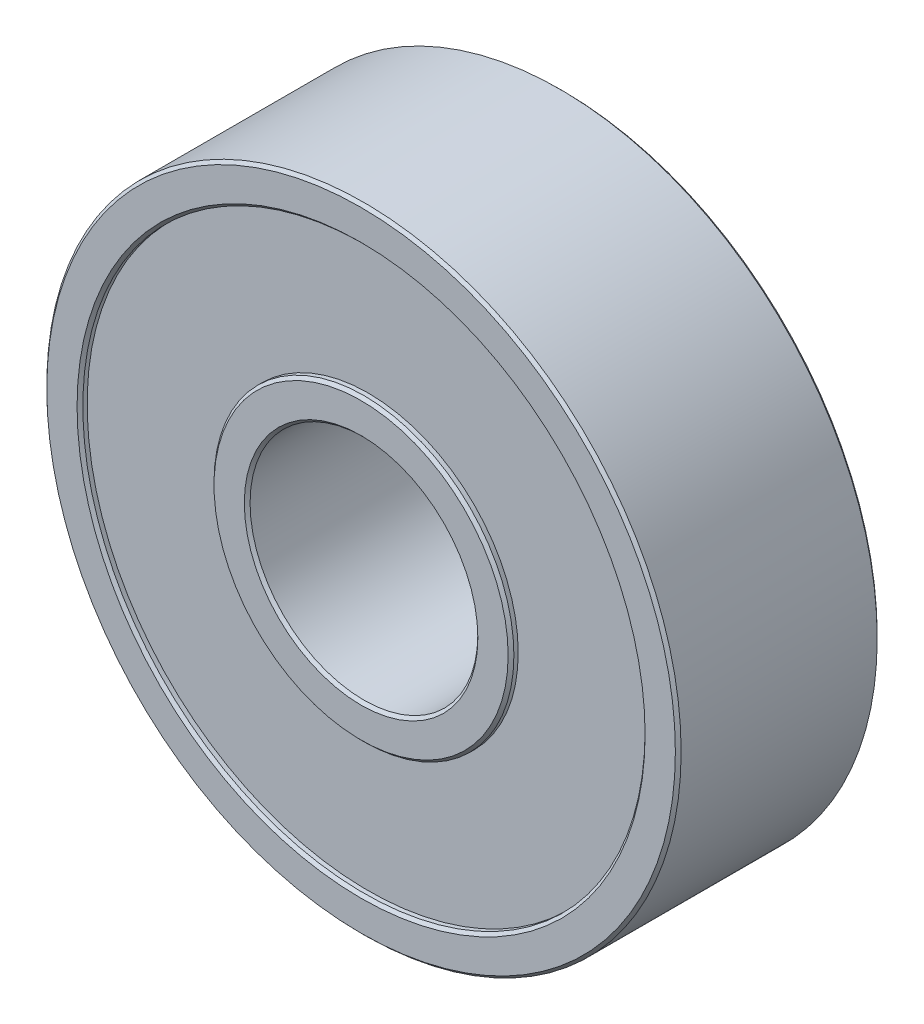
SolidWorks part; units mm, degrees
ref_plane "Front Plane" through (0, 0, 0) normal (0, 0, 1) x (1, 0, 0)
ref_plane "Top Plane" through (0, 0, 0) normal (0, 1, 0) x (1, 0, 0)
ref_plane "Right Plane" through (0, 0, 0) normal (1, 0, 0) x (0, 0, -1)
sketch "Sketch1" plane through (0, 0, 0) normal (0, 0, 1) x (1, 0, 0)
  circle A0 centre (0, 0) radius 3.95
  circle A1 centre (0, 0) radius 11
  dimension "D1" = 7.9
  dimension "D2" = 22
extrude "Boss-Extrude1" add sketch "Sketch1" along normal blind 3.5 and the other way blind 3.5
sketch "Sketch2" plane through (0, 0, 0) normal (0, 0, 1) x (1, 0, 0)
  circle A2 centre (0, 0) radius 5.2
  circle A3 centre (0, 0) radius 5.2
  circle A5 centre (0, 0) radius 9.75
  circle A6 centre (0, 0) radius 9.75
  dimension "D1" = 1.25
  dimension "D2" = 1.25
extrude "Cut-Extrude1" cut sketch "Sketch2" along normal blind 0.25 from surface starting at face at (3.95, 0, -3.5)
extrude "Cut-Extrude2" cut sketch "Sketch2<2>" against normal blind 0.25 from surface starting at face at (11, 0, 3.5)
sketch "Sketch2<2>" plane through (0, 0, 0) normal (0, 0, 1) x (1, 0, 0) same geometry as "Sketch2"
chamfer "Chamfer1" distance 0.1 angle 45 8 edges at (3.95, 0, -3.5) (5.2, 0, -3.5) (9.75, 0, -3.5) (11, 0, -3.5) (5.2, 0, 3.5) (3.95, 0, 3.5) (11, 0, 3.5) (9.75, 0, 3.5)
equation "\"BearingID\"= 7.9"
equation "\"D1@Sketch1\"=\"BearingID\""
equation "\"BearingOD\" = 22"
equation "\"D2@Sketch1\"=\"BearingOD\""
equation "\"BearingThickness\" = 7"
equation "\"D1@Boss-Extrude1\"=\"BearingThickness\"/2"
equation "\"D2@Boss-Extrude1\"=\"BearingThickness\"/2"
